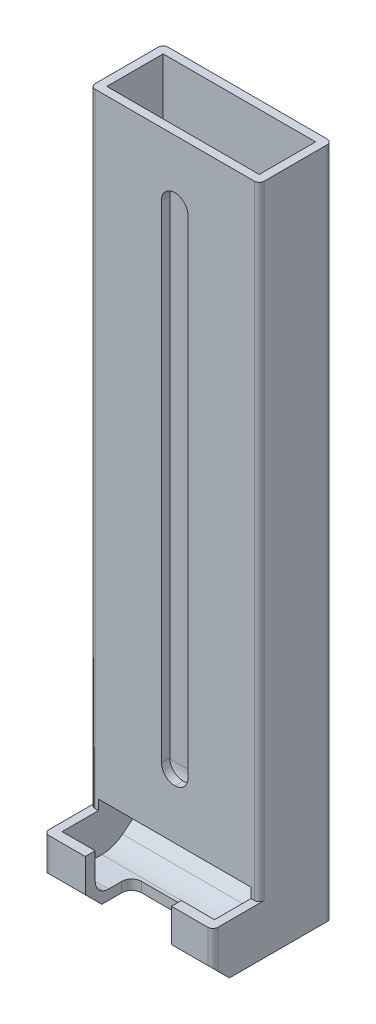
SolidWorks part; units mm, degrees
ref_plane "Front Plane" through (0, 0, 0) normal (0, 0, 1) x (1, 0, 0)
ref_plane "Top Plane" through (0, 0, 0) normal (0, 1, 0) x (1, 0, 0)
ref_plane "Right Plane" through (0, 0, 0) normal (1, 0, 0) x (0, 0, -1)
sketch "Sketch1" plane through (0, 0, 0) normal (0, 1, 0) x (1, 0, 0)
  line L1 (23, -8.5) -> (-23, -8.5)
  line L2 (23, -8.5) -> (23, 8.5)
  line L3 (23, 8.5) -> (-23, 8.5)
  line L4 (-23, -8.5) -> (-23, 8.5)
  line L5 (23, -8.5) -> (-23, 8.5) construction
  line L6 (23, 8.5) -> (-23, -8.5) construction
  line L7 (25.5, -11) -> (-25.5, -11)
  line L8 (25.5, -11) -> (25.5, 11)
  line L9 (25.5, 11) -> (-25.5, 11)
  line L10 (-25.5, -11) -> (-25.5, 11)
  line L11 (25.5, -11) -> (-25.5, 11) construction
  line L12 (25.5, 11) -> (-25.5, -11) construction
  point P0 (0, 0)
  point P6 (0, 0)
  dimension "D1" = 17
  dimension "D2" = 46
  dimension "D3" = 2.5
  dimension "D4" = 2.5
extrude "Boss-Extrude1" add sketch "Sketch1" along normal blind 200
sketch "Sketch2" plane through (0, 0, 0) normal (0, -1, 0) x (1, 0, 0)
  line L1 (25.5, -11) -> (-25.5, -11)
  line L2 (25.5, -11) -> (25.5, 11)
  line L4 (-25.5, -11) -> (-25.5, 11)
  line L5 (25.5, -11) -> (-25.5, 11) construction
  line L6 (25.5, 11) -> (-25.5, -11) construction
  line L9 (25.5, 11) -> (-25.5, 11)
  point P0 (0, 0)
extrude "Boss-Extrude2" add sketch "Sketch2" along normal blind 3
sketch "Sketch5" plane through (25.5, 0, 0) normal (1, 0, 0) x (0, 0, -1)
  line L0 (11, 200) -> (11, -3) construction
  line L3 (20.95, 24.3602) -> (11, 29)
  line L13 (20.95, 17) -> (20.95, 24.3602)
  line L15 (11.25, 18.5) -> (11.25, 17)
  line L16 (11.25, 17) -> (11, 17)
  line L20 (16.95, 18.5) -> (16.95, 17)
  line L21 (16.95, 17) -> (20.95, 17)
  line L22 (11, 29) -> (11, 17)
  line L23 (11, -3) -> (-11, -3) construction
  arc A6 (16.95, 18.5) -> (11.25, 18.5) centre (14.1, 19.4367) ccw
  dimension "D1" = 3
  dimension "D6" = 3.1
  dimension "D2" = 0.25
  dimension "D3" = 12
  dimension "D4" = 1.5
  dimension "D5" = 65
  dimension "D7" = 20
  dimension "D8" = 4
extrude "Boss-Extrude3" add sketch "Sketch5" against normal blind 35 from offset 11 offset against normal yes
chamfer "Chamfer1" distance 0.25 angle 45 2 edges at (-3, 17, -16.95) (-3, 17, -11.25)
pattern_linear "LPattern1" count 2 spacing 58.25 along (0, 1, 0) of "Boss-Extrude3"
sketch "Sketch9" plane through (0, 0, 8.5) normal (0, 0, -1) x (-1, 0, 0)
  line L0 (23, 200) -> (23, 0) construction
  line L1 (-23, 0) -> (23, 0)
  line L2 (-23, 0) -> (-23, 15)
  line L3 (-23, 15) -> (23, 15)
  line L4 (23, 0) -> (23, 15)
  dimension "D1" = 15
extrude "Cut-Extrude1" cut sketch "Sketch9" against normal through all
chamfer "Chamfer2" distance 12 distance2 15 1 edges at (0, 0, -8.5) first distance on face at (0, 100, -8.5)
sketch "Sketch10" plane through (25.5, 0, 0) normal (1, 0, 0) x (0, 0, -1)
  line L0 (-11, -3) -> (-25, -3)
  line L1 (-25, -3) -> (-25, 12)
  line L2 (-25, 12) -> (-11, 12)
  line L3 (-11, 200) -> (-11, -3) construction
  line L4 (-11, 12) -> (-11, -3)
  dimension "D1" = 14
  dimension "D2" = 15
extrude "Boss-Extrude4" add sketch "Sketch10" against normal up to surface (2.5 mm away) up to face at (23, 63.1429, 4.0714)
sketch "Sketch11" plane through (23, 0, 0) normal (-1, 0, 0) x (0, 0, 1)
  line L0 (11, 0) -> (22, 0)
  line L1 (22, 0) -> (22, 12)
  line L2 (11, 12) -> (25, 12) construction
  line L3 (22, 12) -> (25, 12)
  line L4 (25, 12) -> (25, -3)
  line L5 (25, -3) -> (11, -3)
  line L6 (11, -3) -> (11, 0)
  dimension "D1" = 3
extrude "Boss-Extrude5" add sketch "Sketch11" along normal blind 10
ref_plane "Plane1" through (0, 0, 0) normal (1, 0, 0) x (0, 0, -1)
mirror "Mirror1" about plane through (0, 0, 0) normal (1, 0, 0) of "Boss-Extrude5"
sketch "Sketch12" plane through (-23, 0, 0) normal (-1, 0, 0) x (0, 0, 1)
  line L1 (11, -3) -> (25, -3)
  line L2 (11, -3) -> (11, 12)
  line L3 (11, 12) -> (25, 12)
  line L4 (25, -3) -> (25, 12)
extrude "Boss-Extrude6" add sketch "Sketch12" along normal up to surface (2.5 mm away) up to face at (-25.5, 98.5, 0)
sketch "Sketch13" plane through (0, 0, 11) normal (0, 0, 1) x (1, 0, 0)
  line L0 (-25.5, 200) -> (25.5, 200) construction
  line L1 (4, 30) -> (-4, 30)
  line L2 (4, 30) -> (4, 185)
  line L3 (4, 185) -> (-4, 185)
  line L4 (-4, 30) -> (-4, 185)
  line L5 (4, 30) -> (-4, 185) construction
  line L6 (4, 185) -> (-4, 30) construction
  line L7 (-23, 15) -> (23, 15) construction
  point P0 (0, 107.5)
  dimension "D1" = 15
  dimension "D2" = 15
  dimension "D3" = 8
extrude "Cut-Extrude2" cut sketch "Sketch13" against normal up to surface (2.5 mm away) up to face at (0, 107.5, 8.5)
fillet "Fillet11" radius 4 4 edges at (-4, 185, 9.75) (4, 185, 9.75) (-4, 30, 9.75) (4, 30, 9.75)
fillet "Fillet7" radius 4 2 edges at (18, 0, 22) (-18, 0, 22)
chamfer "Chamfer3" distance 5 angle 45 2 edges at (19.25, -3, 25) (-19.25, -3, 25)
fillet "Fillet8" radius 1.5 6 edges at (-25.5, 7, 25) (25.5, 7, 25) (25.5, 98.5, -11) (-25.5, 98.5, -11) (-25.5, 106, 11) (25.5, 106, 11)
fillet "Fillet9" radius 3 2 edges at (13, -1.5, 11) (-13, -1.5, 11)
fillet "Fillet10" radius 10 2 edges at (0, 0, 6.5) (0, 12, -8.5)
sketch "Sketch14" plane through (-23, 0, 0) normal (1, 0, 0) x (0, 0, -1)
  line L0 (-8.5, 15) -> (-5, 15)
  line L1 (-5, 15) -> (-8.5, 25)
  line L2 (-8.5, 200) -> (-8.5, 15) construction
  line L3 (-8.5, 25) -> (-8.5, 15)
  dimension "D1" = 3.5
  dimension "D2" = 10
extrude "Boss-Extrude7" add sketch "Sketch14" along normal up to surface (46 mm away) up to face at (23, 40.3506, 7.7312)
fillet "Fillet12" radius 2 4 edges at (14.5, 23, -11) (14.5, 81.25, -11) (-20.5, 23, -11) (-20.5, 81.25, -11)
